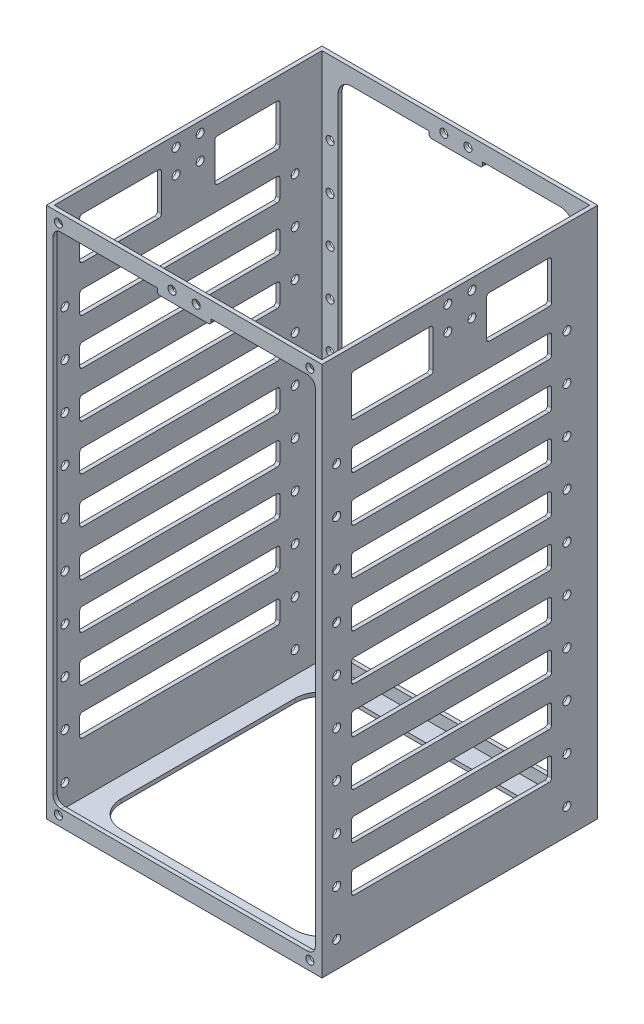
SolidWorks part; units mm, degrees
material "6063-T6"
ref_plane "Front Plane" through (0, 0, 0) normal (0, 0, 1) x (1, 0, 0)
ref_plane "Top Plane" through (0, 0, 0) normal (0, 1, 0) x (1, 0, 0)
ref_plane "Right Plane" through (0, 0, 0) normal (1, 0, 0) x (0, 0, -1)
sketch "Sketch1" plane through (0, 0, 0) normal (0, 1, 0) x (1, 0, 0)
  line L1 (-51.5, -51.5) -> (51.5, -51.5)
  line L2 (-51.5, -51.5) -> (-51.5, 51.5)
  line L3 (-51.5, 51.5) -> (51.5, 51.5)
  line L4 (51.5, -51.5) -> (51.5, 51.5)
  line L5 (-51.5, -51.5) -> (51.5, 51.5) construction
  line L6 (-51.5, 51.5) -> (51.5, -51.5) construction
  line L7 (-32.5, -42.5) -> (32.5, -42.5)
  line L8 (-42.5, -32.5) -> (-42.5, 32.5)
  line L9 (-32.5, 42.5) -> (32.5, 42.5)
  line L10 (42.5, -32.5) -> (42.5, 32.5)
  line L11 (-42.5, -42.5) -> (42.5, 42.5) construction
  line L12 (-42.5, 42.5) -> (42.5, -42.5) construction
  arc A0 (32.5, -42.5) -> (42.5, -32.5) centre (32.5, -32.5) ccw
  arc A1 (32.5, 42.5) -> (42.5, 32.5) centre (32.5, 32.5) cw
  arc A2 (-42.5, 32.5) -> (-32.5, 42.5) centre (-32.5, 32.5) cw
  arc A3 (-32.5, -42.5) -> (-42.5, -32.5) centre (-32.5, -32.5) cw
  point P0 (0, 0)
  point P6 (0, 0)
  dimension "D3" = 10
  dimension "D1" = 103
  dimension "D2" = 42.5
extrude "Boss-Extrude2" add sketch "Sketch1" along normal blind 1.5 contours A3 L7 A0 L10 A1 L9 A2 L8 | L2 L1 L4 L3 region at (0, 0, 0)
sketch "Sketch3" plane through (0, 1.5, 0) normal (0, 1, 0) x (1, 0, 0)
  line L1 (-51.5, -51.5) -> (51.5, -51.5)
  line L2 (-51.5, -51.5) -> (-51.5, 51.5)
  line L3 (-51.5, 51.5) -> (51.5, 51.5)
  line L4 (51.5, -51.5) -> (51.5, 51.5)
  line L5 (-51.5, -51.5) -> (51.5, 51.5) construction
  line L6 (-51.5, 51.5) -> (51.5, -51.5) construction
  line L7 (-50, -50) -> (50, -50)
  line L8 (-50, -50) -> (-50, 50)
  line L9 (-50, 50) -> (50, 50)
  line L10 (50, -50) -> (50, 50)
  line L11 (-50, -50) -> (50, 50) construction
  line L12 (-50, 50) -> (50, -50) construction
  point P0 (0, 0)
  point P7 (0, 0)
  dimension "D1" = 100
extrude "Boss-Extrude3" add sketch "Sketch3" along normal blind 197 contours L8 L7 L10 L9 | L2 L3 L4 L1
sketch "Sketch4" plane through (0, 0, -51.5) normal (0, 0, 1) x (1, 0, 0)
  line L0 (-51.5, 0) -> (51.5, 0) construction
  line L1 (-39, 6) -> (39, 6)
  line L2 (-44, 11) -> (-44, 187.5)
  line L3 (-39, 192.5) -> (39, 192.5)
  line L4 (44, 11) -> (44, 187.5)
  line L5 (-44, 6) -> (44, 192.5) construction
  line L6 (-44, 192.5) -> (44, 6) construction
  line L7 (51.5, 198.5) -> (51.5, 0) construction
  line L8 (-50, 198.5) -> (50, 198.5) construction
  line L9 (-51.5, 198.5) -> (-51.5, 0) construction
  arc A0 (-39, 6) -> (-44, 11) centre (-39, 11) cw
  arc A1 (39, 6) -> (44, 11) centre (39, 11) ccw
  arc A2 (39, 192.5) -> (44, 187.5) centre (39, 187.5) cw
  arc A3 (-44, 187.5) -> (-39, 192.5) centre (-39, 187.5) cw
  point P0 (0, 99.25)
  dimension "D5" = 5
  dimension "D1" = 6
  dimension "D2" = 7.5
  dimension "D3" = 6
  dimension "D4" = 7.5
extrude "Cut-Extrude1" cut sketch "Sketch4" along normal up to surface (1.5 mm away) up to face at (0, 100, -50)
sketch "Sketch5" plane through (0, 0, 51.5) normal (0, 0, 1) x (1, 0, 0)
  line L0 (-51.5, 198.5) -> (51.5, 198.5) construction
  line L1 (-46, 6) -> (46, 6)
  line L2 (-49, 9) -> (-49, 189.5)
  line L3 (-46, 192.5) -> (46, 192.5)
  line L4 (49, 9) -> (49, 189.5)
  line L5 (-49, 6) -> (49, 192.5) construction
  line L6 (-49, 192.5) -> (49, 6) construction
  line L7 (-51.5, 1.5) -> (51.5, 1.5) construction
  line L8 (-51.5, 198.5) -> (-51.5, 0) construction
  line L9 (51.5, 198.5) -> (51.5, 0) construction
  arc A0 (46, 6) -> (49, 9) centre (46, 9) ccw
  arc A1 (-46, 6) -> (-49, 9) centre (-46, 9) cw
  arc A2 (46, 192.5) -> (49, 189.5) centre (46, 189.5) cw
  arc A3 (-49, 189.5) -> (-46, 192.5) centre (-46, 189.5) cw
  point P0 (0, 99.25)
  dimension "D5" = 3
  dimension "D1" = 6
  dimension "D2" = 4.5
  dimension "D3" = 2.5
  dimension "D4" = 2.5
sketch "Sketch6" plane through (51.5, 0, 0) normal (1, 0, 0) x (0, 0, -1)
  line L0 (-51.5, 6) -> (-51.5, 192.5) construction
  line L2 (-51.5, 0) -> (51.5, 0) construction
  circle A0 centre (-46, 9.75) radius 1.5
  circle A1 centre (40, 9.75) radius 1.5
  circle A2 centre (-46, 26.85) radius 1.5
  circle A3 centre (40, 26.85) radius 1.5
  circle A4 centre (-46, 43.95) radius 1.5
  circle A5 centre (40, 43.95) radius 1.5
  circle A6 centre (-46, 61.05) radius 1.5
  circle A7 centre (40, 61.05) radius 1.5
  circle A8 centre (-46, 78.15) radius 1.5
  circle A9 centre (40, 78.15) radius 1.5
  circle A10 centre (-46, 95.25) radius 1.5
  circle A11 centre (40, 95.25) radius 1.5
  circle A12 centre (-46, 112.35) radius 1.5
  circle A13 centre (40, 112.35) radius 1.5
  circle A14 centre (-46, 129.45) radius 1.5
  circle A15 centre (40, 129.45) radius 1.5
  circle A16 centre (-46, 146.55) radius 1.5
  circle A17 centre (40, 146.55) radius 1.5
  circle A18 centre (-46, 163.65) radius 1.5
  circle A19 centre (40, 163.65) radius 1.5
  dimension "D4" = 3
  dimension "D5" = 3
  dimension "D1" = 5.5
  dimension "D2" = 86
  dimension "D3" = 9.75
  dimension "D7" = 17.1
  dimension "D9" = 17.1
  dimension "D6" = 9
  dimension "D8" = 2
extrude "Cut-Extrude2" cut sketch "Sketch6" against normal through all
extrude "Cut-Extrude3" cut sketch "Sketch5" against normal up to surface (1.5 mm away) up to face at (0, 100, 50)
sketch "Sketch7" plane through (51.5, 0, 0) normal (1, 0, 0) x (0, 0, -1)
  line L0 (-40.5, 38.95) -> (-40.5, 45.45)
  line L1 (-39.5, 20.85) -> (33.25, 20.85)
  line L2 (-40.5, 21.85) -> (-40.5, 28.35)
  line L3 (-39.5, 29.35) -> (33.25, 29.35)
  line L4 (34.25, 21.85) -> (34.25, 28.35)
  line L5 (-40.5, 20.85) -> (34.25, 29.35) construction
  line L6 (-40.5, 29.35) -> (34.25, 20.85) construction
  line L7 (-40.5, 158.65) -> (-40.5, 165.15)
  line L8 (-39.5, 37.95) -> (33.25, 37.95)
  line L9 (34.25, 38.95) -> (34.25, 45.45)
  line L10 (-39.5, 46.45) -> (33.25, 46.45)
  line L11 (-40.5, 56.05) -> (-40.5, 62.55)
  line L12 (-39.5, 55.05) -> (33.25, 55.05)
  line L13 (34.25, 56.05) -> (34.25, 62.55)
  line L14 (-39.5, 63.55) -> (33.25, 63.55)
  line L15 (-40.5, 73.15) -> (-40.5, 79.65)
  line L16 (-39.5, 72.15) -> (33.25, 72.15)
  line L17 (34.25, 73.15) -> (34.25, 79.65)
  line L18 (-39.5, 80.65) -> (33.25, 80.65)
  line L19 (-40.5, 90.25) -> (-40.5, 96.75)
  line L20 (-39.5, 89.25) -> (33.25, 89.25)
  line L21 (34.25, 90.25) -> (34.25, 96.75)
  line L22 (-39.5, 97.75) -> (33.25, 97.75)
  line L23 (-40.5, 107.35) -> (-40.5, 113.85)
  line L24 (-39.5, 106.35) -> (33.25, 106.35)
  line L25 (34.25, 107.35) -> (34.25, 113.85)
  line L26 (-39.5, 114.85) -> (33.25, 114.85)
  line L27 (-40.5, 124.45) -> (-40.5, 130.95)
  line L28 (-39.5, 123.45) -> (33.25, 123.45)
  line L29 (34.25, 124.45) -> (34.25, 130.95)
  line L30 (-39.5, 131.95) -> (33.25, 131.95)
  line L31 (-40.5, 141.55) -> (-40.5, 148.05)
  line L32 (-39.5, 140.55) -> (33.25, 140.55)
  line L33 (34.25, 141.55) -> (34.25, 148.05)
  line L34 (-39.5, 149.05) -> (33.25, 149.05)
  line L35 (-39.5, 157.65) -> (33.25, 157.65)
  line L36 (34.25, 158.65) -> (34.25, 165.15)
  line L37 (-39.5, 166.15) -> (33.25, 166.15)
  line L38 (-40.5, 141.55) -> (-40.5, 158.65) construction
  circle A0 centre (-46, 9.75) radius 1.5 construction
  arc A1 (33.25, 29.35) -> (34.25, 28.35) centre (33.25, 28.35) cw
  arc A2 (33.25, 20.85) -> (34.25, 21.85) centre (33.25, 21.85) ccw
  arc A3 (-39.5, 20.85) -> (-40.5, 21.85) centre (-39.5, 21.85) cw
  arc A4 (-40.5, 28.35) -> (-39.5, 29.35) centre (-39.5, 28.35) cw
  arc A5 (-40.5, 45.45) -> (-39.5, 46.45) centre (-39.5, 45.45) cw
  arc A6 (-39.5, 37.95) -> (-40.5, 38.95) centre (-39.5, 38.95) cw
  arc A7 (33.25, 37.95) -> (34.25, 38.95) centre (33.25, 38.95) ccw
  arc A8 (33.25, 46.45) -> (34.25, 45.45) centre (33.25, 45.45) cw
  arc A9 (-40.5, 62.55) -> (-39.5, 63.55) centre (-39.5, 62.55) cw
  arc A10 (-39.5, 55.05) -> (-40.5, 56.05) centre (-39.5, 56.05) cw
  arc A11 (33.25, 55.05) -> (34.25, 56.05) centre (33.25, 56.05) ccw
  arc A12 (33.25, 63.55) -> (34.25, 62.55) centre (33.25, 62.55) cw
  arc A13 (-40.5, 79.65) -> (-39.5, 80.65) centre (-39.5, 79.65) cw
  arc A14 (-39.5, 72.15) -> (-40.5, 73.15) centre (-39.5, 73.15) cw
  arc A15 (33.25, 72.15) -> (34.25, 73.15) centre (33.25, 73.15) ccw
  arc A16 (33.25, 80.65) -> (34.25, 79.65) centre (33.25, 79.65) cw
  arc A17 (-40.5, 96.75) -> (-39.5, 97.75) centre (-39.5, 96.75) cw
  arc A18 (-39.5, 89.25) -> (-40.5, 90.25) centre (-39.5, 90.25) cw
  arc A19 (33.25, 89.25) -> (34.25, 90.25) centre (33.25, 90.25) ccw
  arc A20 (33.25, 97.75) -> (34.25, 96.75) centre (33.25, 96.75) cw
  arc A21 (-40.5, 113.85) -> (-39.5, 114.85) centre (-39.5, 113.85) cw
  arc A22 (-39.5, 106.35) -> (-40.5, 107.35) centre (-39.5, 107.35) cw
  arc A23 (33.25, 106.35) -> (34.25, 107.35) centre (33.25, 107.35) ccw
  arc A24 (33.25, 114.85) -> (34.25, 113.85) centre (33.25, 113.85) cw
  arc A25 (-40.5, 130.95) -> (-39.5, 131.95) centre (-39.5, 130.95) cw
  arc A26 (-39.5, 123.45) -> (-40.5, 124.45) centre (-39.5, 124.45) cw
  arc A27 (33.25, 123.45) -> (34.25, 124.45) centre (33.25, 124.45) ccw
  arc A28 (33.25, 131.95) -> (34.25, 130.95) centre (33.25, 130.95) cw
  arc A29 (-40.5, 148.05) -> (-39.5, 149.05) centre (-39.5, 148.05) cw
  arc A30 (-39.5, 140.55) -> (-40.5, 141.55) centre (-39.5, 141.55) cw
  arc A31 (33.25, 140.55) -> (34.25, 141.55) centre (33.25, 141.55) ccw
  arc A32 (33.25, 149.05) -> (34.25, 148.05) centre (33.25, 148.05) cw
  arc A33 (-40.5, 165.15) -> (-39.5, 166.15) centre (-39.5, 165.15) cw
  arc A34 (-39.5, 157.65) -> (-40.5, 158.65) centre (-39.5, 158.65) cw
  circle A35 centre (40, 9.75) radius 1.5 construction
  arc A36 (33.25, 157.65) -> (34.25, 158.65) centre (33.25, 158.65) ccw
  arc A37 (33.25, 166.15) -> (34.25, 165.15) centre (33.25, 165.15) cw
  point P0 (-3.125, 25.1)
  dimension "D5" = 1
  dimension "D3" = 5.75
  dimension "D1" = 8.5
  dimension "D2" = 11.1
  dimension "D4" = 5.5
  dimension "D7" = 8.6
  dimension "D9" = 8.6
  dimension "D6" = 8
  dimension "D8" = 2
extrude "Cut-Extrude4" cut sketch "Sketch7" against normal through all
sketch "Sketch8" plane through (51.5, 0, 0) normal (1, 0, 0) x (0, 0, -1)
  line L7 (-51.5, 198.5) -> (51.5, 198.5) construction
  line L15 (-39.5, 190.5) -> (33.25, 190.5)
  line L16 (-40.5, 189.5) -> (-40.5, 175.75)
  line L17 (-39.5, 174.75) -> (33.25, 174.75)
  line L18 (34.25, 189.5) -> (34.25, 175.75)
  line L19 (33.25, 166.15) -> (-39.5, 166.15) construction
  arc A15 (33.25, 190.5) -> (34.25, 189.5) centre (33.25, 189.5) cw
  arc A16 (33.25, 174.75) -> (34.25, 175.75) centre (33.25, 175.75) ccw
  arc A17 (-40.5, 175.75) -> (-39.5, 174.75) centre (-39.5, 175.75) ccw
  arc A18 (-39.5, 190.5) -> (-40.5, 189.5) centre (-39.5, 189.5) ccw
  circle A19 centre (-46, 163.65) radius 1.5 construction
  circle A20 centre (40, 163.65) radius 1.5 construction
  point P0 (-2.625, 162.85)
  dimension "D6" = 1
  dimension "D2" = 8.6
  dimension "D8" = 8
  dimension "D9" = 5.5
  dimension "D10" = 5.75
extrude "Cut-Extrude5" cut sketch "Sketch8" against normal through all
sketch "Sketch15" plane through (51.5, 0, 0) normal (1, 0, 0) x (0, 0, -1)
  line L0 (-50, 198.5) -> (-50, 1.5) construction
  line L7 (33.25, 190.5) -> (-39.5, 190.5) construction
  line L8 (-10, 190.5) -> (10, 190.5)
  line L9 (-10, 190.5) -> (-10, 174.75)
  line L10 (-10, 174.75) -> (10, 174.75)
  line L11 (10, 190.5) -> (10, 174.75)
  line L12 (-39.5, 174.75) -> (33.25, 174.75) construction
  dimension "D1" = 20
  dimension "D2" = 40
extrude "Boss-Extrude4" add sketch "Sketch15" against normal up to surface (1.5 mm away) up to face at (50, 182.625, 3.125)
sketch "Sketch16" plane through (-51.5, 0, 0) normal (-1, 0, 0) x (0, 0, 1)
  line L7 (-10, 190.5) -> (10, 190.5)
  line L8 (-10, 190.5) -> (-10, 174.75)
  line L9 (-10, 174.75) -> (10, 174.75)
  line L10 (10, 190.5) -> (10, 174.75)
extrude "Boss-Extrude5" add sketch "Sketch16" against normal up to surface (1.5 mm away) up to face at (-50, 182.625, 3.125)
sketch "Sketch9" plane through (51.5, 0, 0) normal (1, 0, 0) x (0, 0, -1)
  line L0 (-51.5, 198.5) -> (51.5, 198.5) construction
  line L2 (-11.0428, 190) -> (9.2919, 190) construction
  line L3 (-50, 198.5) -> (-50, 1.5) construction
  circle A0 centre (-4.5, 194.5) radius 1.5
  circle A1 centre (4.5, 194.5) radius 1.5
  circle A2 centre (4.5, 185.5) radius 1.5
  circle A3 centre (-4.5, 185.5) radius 1.5
  dimension "D1" = 3
  dimension "D3" = 9
  dimension "D5" = 3
  dimension "D2" = 4
  dimension "D4" = 45.5
  dimension "D6" = 4.5
extrude "Cut-Extrude6" cut sketch "Sketch9" against normal through all
fillet "Fillet1" radius 1 8 edges at (-50.75, 174.75, 10) (-50.75, 190.5, 10) (-50.75, 190.5, -10) (-50.75, 174.75, -10) (50.75, 190.5, 10) (50.75, 174.75, 10) (50.75, 174.75, -10) (50.75, 190.5, -10)
sketch "Sketch18" plane through (0, 0, -51.5) normal (0, 0, -1) x (-1, 0, 0)
  line L0 (-39, 192.5) -> (39, 192.5) construction
  line L1 (-10, 192.5) -> (10, 192.5)
  line L2 (-10, 192.5) -> (-10, 191.5)
  line L3 (-9, 190.5) -> (9, 190.5)
  line L4 (10, 192.5) -> (10, 191.5)
  line L6 (-50, 198.5) -> (-50, 1.5) construction
  arc A0 (9, 190.5) -> (10, 191.5) centre (9, 191.5) ccw
  arc A1 (-10, 191.5) -> (-9, 190.5) centre (-9, 191.5) ccw
  point P4 (-10, 192)
  dimension "D3" = 1
  dimension "D1" = 2
  dimension "D2" = 20
  dimension "D4" = 40
extrude "Boss-Extrude7" add sketch "Sketch18" against normal up to surface (1.5 mm away) up to face at (0, 99.25, -50)
sketch "Sketch17" plane through (0, 0, 51.5) normal (0, 0, 1) x (1, 0, 0)
  line L0 (46, 192.5) -> (-46, 192.5) construction
  line L1 (-10, 192.5) -> (10, 192.5)
  line L2 (-10, 192.5) -> (-10, 191.5)
  line L3 (-9, 190.5) -> (9, 190.5)
  line L4 (10, 192.5) -> (10, 191.5)
  line L5 (-50, 198.5) -> (-50, 1.5) construction
  arc A0 (9, 190.5) -> (10, 191.5) centre (9, 191.5) ccw
  arc A1 (-10, 191.5) -> (-9, 190.5) centre (-9, 191.5) ccw
  dimension "D4" = 1
  dimension "D1" = 20
  dimension "D2" = 40
  dimension "D3" = 2
extrude "Boss-Extrude6" add sketch "Sketch17" against normal up to surface (1.5 mm away) up to face at (0, 99.25, 50)
sketch "Sketch19" plane through (0, 0, 51.5) normal (0, 0, 1) x (1, 0, 0)
  line L0 (0, 198.5) -> (0, 190.5) construction
  line L1 (-9, 190.5) -> (9, 190.5) construction
  line L3 (-51.5, 198.5) -> (51.5, 198.5) construction
  circle A0 centre (-4.5, 194.5) radius 1.5
  circle A1 centre (4.5, 194.5) radius 1.5
  dimension "D1" = 3
  dimension "D2" = 4
  dimension "D3" = 4.5
extrude "Cut-Extrude7" cut sketch "Sketch19" against normal through all
sketch "Sketch20" plane through (0, 0, 51.5) normal (0, 0, 1) x (1, 0, 0)
  line L1 (-51.5, 0) -> (51.5, 0) construction
  line L2 (0, 198.5) -> (0, 0) construction
  line L3 (-51.5, 198.5) -> (51.5, 198.5) construction
  line L4 (-50, 198.5) -> (-50, 1.5) construction
  line L5 (-50, 198.5) -> (-50, 1.5) construction
  circle A0 centre (-46.98, 3.5) radius 1.5
  circle A1 centre (-46.98, 195) radius 1.5
  circle A2 centre (46.98, 3.5) radius 1.5
  circle A3 centre (46.98, 195) radius 1.5
  dimension "D1" = 3
  dimension "D4" = 3
  dimension "D2" = 3.02
  dimension "D3" = 3.5
  dimension "D5" = 3.02
  dimension "D6" = 3.5
extrude "Cut-Extrude8" cut sketch "Sketch20" against normal up to surface (1.5 mm away) up to face at (-6, 194.5, 50)
sketch "Sketch23" plane through (0, 0, -51.5) normal (0, 0, -1) x (-1, 0, 0)
  line L0 (-51.5, 198.5) -> (-51.5, 0) construction
  line L1 (51.5, 0) -> (-51.5, 0) construction
  line L2 (0, 198.5) -> (0, 0) construction
  line L3 (51.5, 198.5) -> (-51.5, 198.5) construction
  circle A0 centre (-47, 17.05) radius 1.5
  circle A2 centre (-47, 34.15) radius 1.5
  circle A3 centre (-47, 51.25) radius 1.5
  circle A4 centre (-47, 68.35) radius 1.5
  circle A5 centre (-47, 85.45) radius 1.5
  circle A6 centre (-47, 102.55) radius 1.5
  circle A7 centre (-47, 119.65) radius 1.5
  circle A8 centre (-47, 136.75) radius 1.5
  circle A9 centre (-47, 153.85) radius 1.5
  circle A10 centre (-47, 170.95) radius 1.5
  circle A11 centre (47, 170.95) radius 1.5
  circle A12 centre (47, 153.85) radius 1.5
  circle A13 centre (47, 136.75) radius 1.5
  circle A14 centre (47, 119.65) radius 1.5
  circle A15 centre (47, 102.55) radius 1.5
  circle A16 centre (47, 85.45) radius 1.5
  circle A17 centre (47, 68.35) radius 1.5
  circle A18 centre (47, 51.25) radius 1.5
  circle A19 centre (47, 34.15) radius 1.5
  circle A20 centre (47, 17.05) radius 1.5
  dimension "D1" = 3
  dimension "D2" = 4.5
  dimension "D3" = 17.05
  dimension "D5" = 17.1
  dimension "D4" = 10
extrude "Cut-Extrude10" cut sketch "Sketch23" against normal up to surface (1.5 mm away) up to face at (-6, 194.5, -50)
